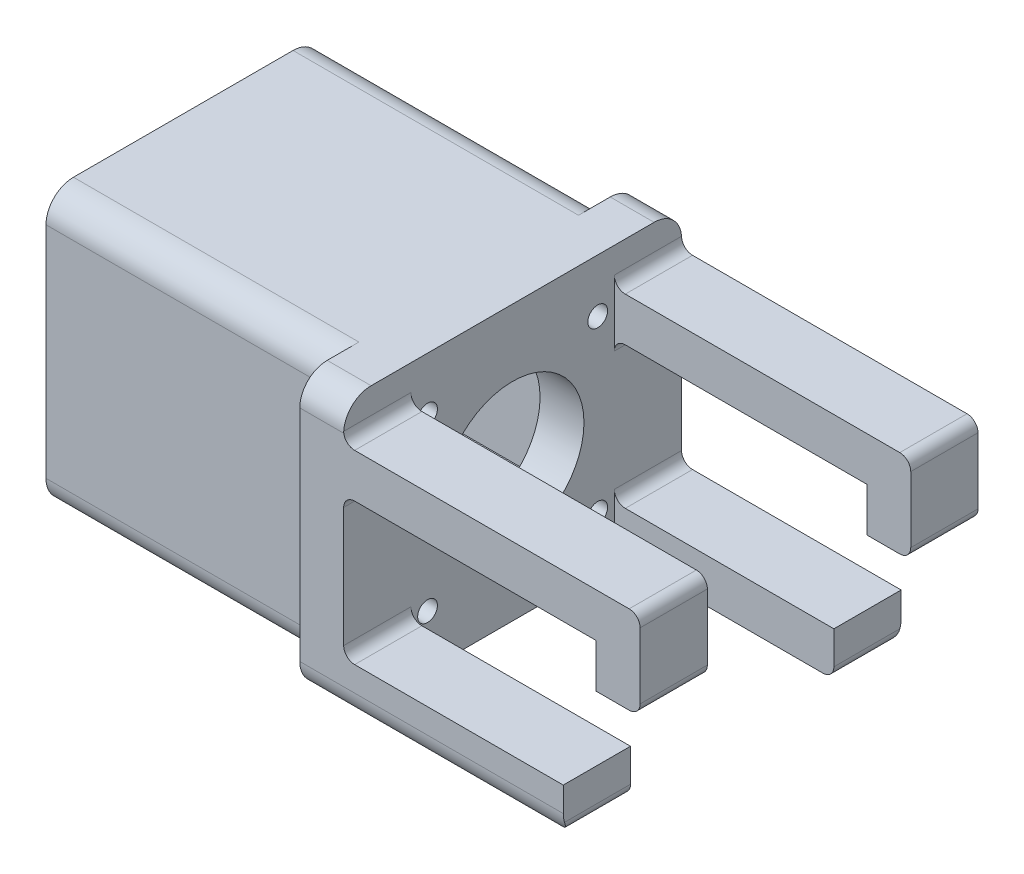
SolidWorks part; units mm, degrees
ref_plane "Front Plane" through (0, 0, 0) normal (0, 0, 1) x (1, 0, 0)
ref_plane "Top Plane" through (0, 0, 0) normal (0, 1, 0) x (1, 0, 0)
ref_plane "Right Plane" through (0, 0, 0) normal (1, 0, 0) x (0, 0, -1)
sketch "Sketch1" plane through (0, 0, 0) normal (1, 0, 0) x (0, 0, -1)
  line L0 (0, 0) -> (61.55, 0)
  line L1 (0, 0) -> (0, 50)
  line L2 (0, 50) -> (61.55, 50)
  line L3 (61.55, 50) -> (61.55, 0)
  line L4 (30.775, 50) -> (30.775, 0) construction
  line L5 (0, 43.3) -> (61.55, 43.3) construction
  line L6 (0, 35.3) -> (12.25, 35.3)
  line L7 (12.25, 35.3) -> (12.25, 43.3)
  line L8 (49.3, 43.3) -> (49.3, 35.3)
  line L9 (49.3, 35.3) -> (61.55, 35.3)
  line L10 (0, 9.5) -> (61.55, 9.5) construction
  line L11 (0, 1.5) -> (12.25, 1.5)
  line L12 (12.25, 1.5) -> (12.25, 9.5)
  line L13 (61.55, 1.5) -> (49.3, 1.5)
  line L14 (49.3, 1.5) -> (49.3, 9.5)
  line L15 (30.775, 24.8) -> (15.2752, 40.2998) construction
  line L16 (12.25, 43.3) -> (0, 43.3)
  line L17 (0, 43.3) -> (0, 35.3)
  line L18 (49.3, 43.3) -> (61.55, 43.3)
  line L19 (61.55, 43.3) -> (61.55, 35.3)
  line L20 (0, 1.5) -> (0, 9.5)
  line L21 (0, 9.5) -> (12.25, 9.5)
  line L22 (49.3, 9.5) -> (61.55, 9.5)
  line L23 (61.55, 9.5) -> (61.55, 1.5)
  line L24 (0, 3.5) -> (61.55, 3.5) construction
  line L25 (0, 46.5) -> (61.55, 46.5) construction
  line L26 (9.275, 50) -> (9.275, 0) construction
  line L27 (52.275, 50) -> (52.275, 0) construction
  line L28 (5.775, 50) -> (5.775, 0) construction
  line L29 (55.775, 50) -> (55.775, 0) construction
  circle A0 centre (30.775, 24.8) radius 13
  circle A1 centre (15.2752, 40.2998) radius 1.8
  circle A2 centre (46.2748, 40.2998) radius 1.8
  circle A3 centre (46.2748, 9.3002) radius 1.8
  circle A4 centre (15.2752, 9.3002) radius 1.8
  dimension "D10" = 26
  dimension "D11" = 3.6
  dimension "D1" = 61.55
  dimension "D2" = 24.8
  dimension "D3" = 50
  dimension "D4" = 18.5
  dimension "D5" = 8
  dimension "D6" = 12.25
  dimension "D7" = 12.25
  dimension "D8" = 15.3
  dimension "D9" = 8
  dimension "D12" = 21.92
  dimension "D13" = 4
  dimension "D15" = 135
  dimension "D14" = 21.92
  dimension "D16" = 15.4998
  dimension "D17" = 3.5
  dimension "D18" = 3.5
  dimension "D19" = 21.5
  dimension "D20" = 21.5
  dimension "D21" = 25
  dimension "D22" = 25
extrude "Boss-Extrude1" add sketch "Sketch1" along normal blind 54 contours L7 L16 L1 L6 | L18 L8 L9 L3 region at (0, 39.3, -6.125) region at (0, 39.3, -55.425)
extrude "Boss-Extrude7" add sketch "Sketch1<7>" along normal blind 40 contours L21 L1 L11 L12 | L22 L14 L13 L3 region at (0, 5.5, -6.125) region at (0, 5.5, -55.425)
sketch "Sketch1<7>" plane through (0, 0, 0) normal (1, 0, 0) x (0, 0, -1) same geometry as "Sketch1"
extrude "Boss-Extrude2" add sketch "Sketch1<3>" against normal blind 8 contours L14 L22 L3 L9 L8 L18 L2 L1 L16 L7 L6 L21 L12 L11 L0 L13 A4 A3 A2 A1 A0 | L21 L12 L11 L20 | L17 L6 L7 L16 | L23 L13 L14 L22 | L19 L9 L8 L18 region at (0, 0.75, -0.793)
sketch "Sketch1<3>" plane through (0, 0, 0) normal (1, 0, 0) x (0, 0, -1) same geometry as "Sketch1"
fillet "Fillet1" radius 2 6 edges at (0, 43.3, -55.425) (0, 43.3, -6.125) (0, 35.3, -55.425) (0, 35.3, -6.125) (0, 9.5, -55.425) (0, 9.5, -6.125)
sketch "Sketch2" plane through (0, 35.3, 0) normal (0, -1, 0) x (1, 0, 0)
  line L0 (54, 0) -> (54, -12.25)
  line L1 (54, -12.25) -> (46, -12.25)
  line L3 (46, -12.25) -> (46, 0)
  line L5 (46, 0) -> (54, 0)
  line L6 (54, -49.3) -> (54, -61.55)
  line L7 (54, -61.55) -> (46, -61.55)
  line L9 (46, -61.55) -> (46, -49.3)
  line L11 (46, -49.3) -> (54, -49.3)
  line L12 (54, 0) -> (54, -12.25) construction
  line L13 (54, -12.25) -> (2, -12.25) construction
  line L14 (54, -61.55) -> (2, -61.55) construction
  point P6 (55.6907, -2.1285)
  point P7 (0, 0)
  point P9 (54, 0)
  point P10 (54, -11.1774)
  point P14 (0, 0)
  point P16 (54, -12.25)
  point P20 (46, -12.25)
  point P24 (54, -12.25)
  point P25 (54, -9.4308)
  point P26 (54, -10.2104)
  point P28 (55.7674, -52.5128)
  point P29 (54, -49.3)
  point P31 (54, -58.6548)
  point P33 (46, -58.6083)
  dimension "D1" = 8
extrude "Boss-Extrude3" add sketch "Sketch2" along normal blind 8
fillet "Fillet2" radius 5 4 edges at (-4, 50, -61.55) (-4, 0, -61.55) (-4, 0, 0) (-4, 50, 0)
fillet "Fillet3" radius 2 6 edges at (54, 27.3, -6.125) (54, 43.3, -55.425) (54, 43.3, -6.125) (54, 27.3, -55.425) (40, 1.5, -54.7104) (40, 1.5, -6.8396)
sketch "Sketch3" plane through (-8, 0, 0) normal (-1, 0, 0) x (0, 0, 1)
  line L0 (-55.775, 50) -> (-5.775, 50)
  line L1 (-5.775, 50) -> (-5.775, 0)
  line L2 (-5.775, 0) -> (-55.775, 0)
  line L3 (-55.775, 0) -> (-55.775, 50)
  line L4 (-52.275, 46.5) -> (-9.2325, 46.5)
  line L5 (0, 46.5) -> (-61.55, 46.5) construction
  line L6 (-52.275, 50) -> (-52.275, 0) construction
  line L7 (-9.2325, 46.5) -> (-9.275, 3.5)
  line L8 (0, 3.5) -> (-61.55, 3.5) construction
  line L9 (-9.275, 50) -> (-9.275, 0) construction
  line L10 (-9.275, 3.5) -> (-52.275, 3.5)
  line L11 (-52.275, 3.5) -> (-52.275, 46.5)
extrude "Boss-Extrude4" add sketch "Sketch3" along normal blind 52
fillet "Fillet7" radius 5 4 edges at (-34, 0, -55.775) (-34, 50, -55.775) (-34, 0, -5.775) (-34, 50, -5.775)
sketch "Sketch4" plane through (0, 0, 0) normal (0, -1, 0) x (1, 0, 0)
  line L0 (-60, -30.775) -> (0, -30.775) construction
  line L1 (-60, -50.775) -> (-60, -10.775) construction
  line L2 (0, -5) -> (0, -56.55) construction
  line L3 (-60, -28.775) -> (-40, -28.775)
  line L4 (-40, -28.775) -> (-40, -32.775)
  line L5 (-40, -32.775) -> (-60, -32.775)
  line L6 (-60, -32.775) -> (-60, -28.775)
  point P8 (-40, -30.775)
  dimension "D1" = 20
  dimension "D2" = 4
extrude "Cut-Extrude1" cut sketch "Sketch4" against normal up to next (3.5 mm away) draft 30 draft outward yes
